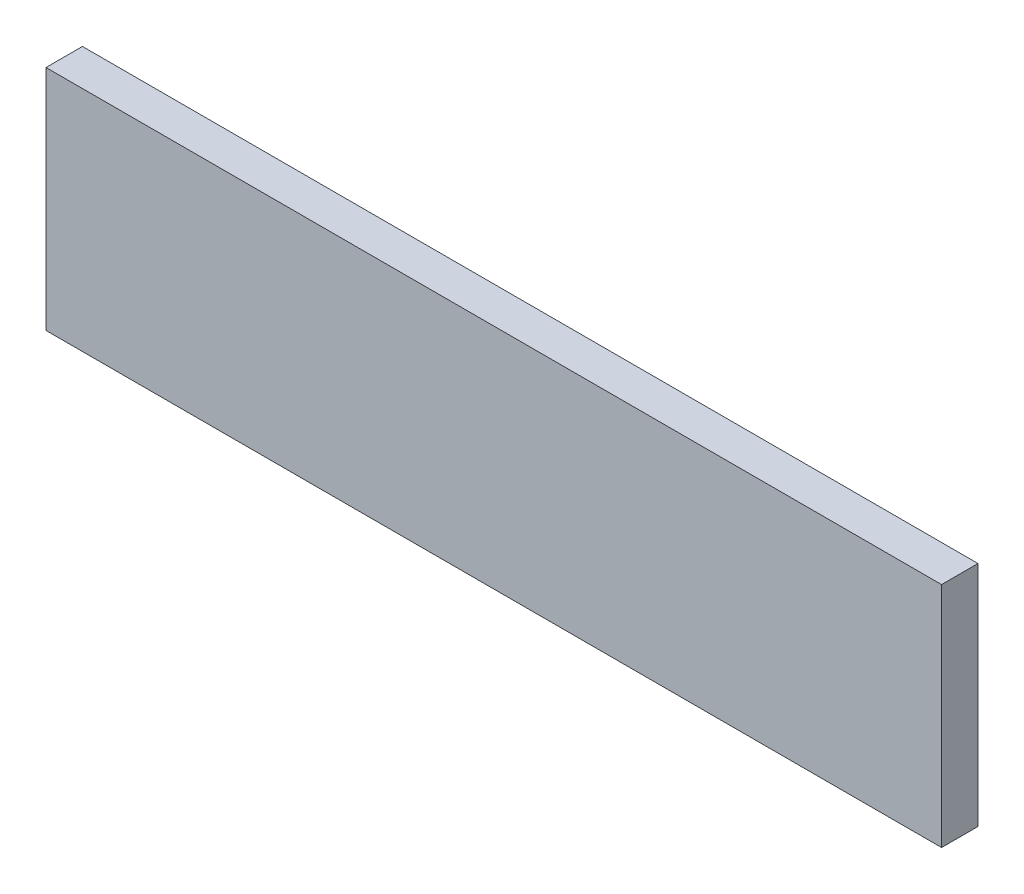
SolidWorks part; units mm, degrees
ref_plane "Front Plane" through (0, 0, 0) normal (0, 0, 1) x (1, 0, 0)
ref_plane "Top Plane" through (0, 0, 0) normal (0, 1, 0) x (1, 0, 0)
ref_plane "Right Plane" through (0, 0, 0) normal (1, 0, 0) x (0, 0, -1)
sketch "Sketch1" plane through (0, 0, 0) normal (0, 0, 1) x (1, 0, 0)
  line L1 (234.05, 0) -> (-234.05, 0)
  line L2 (234.05, 0) -> (234.05, 119.05)
  line L3 (234.05, 119.05) -> (-234.05, 119.05)
  line L4 (-234.05, 0) -> (-234.05, 119.05)
  line L5 (-300, 119.05) -> (300, 119.05) construction
  dimension "D1" = 119.05
  dimension "D2" = 468.1
extrude "Boss-Extrude1" add sketch "Sketch1" along normal blind 19.05
